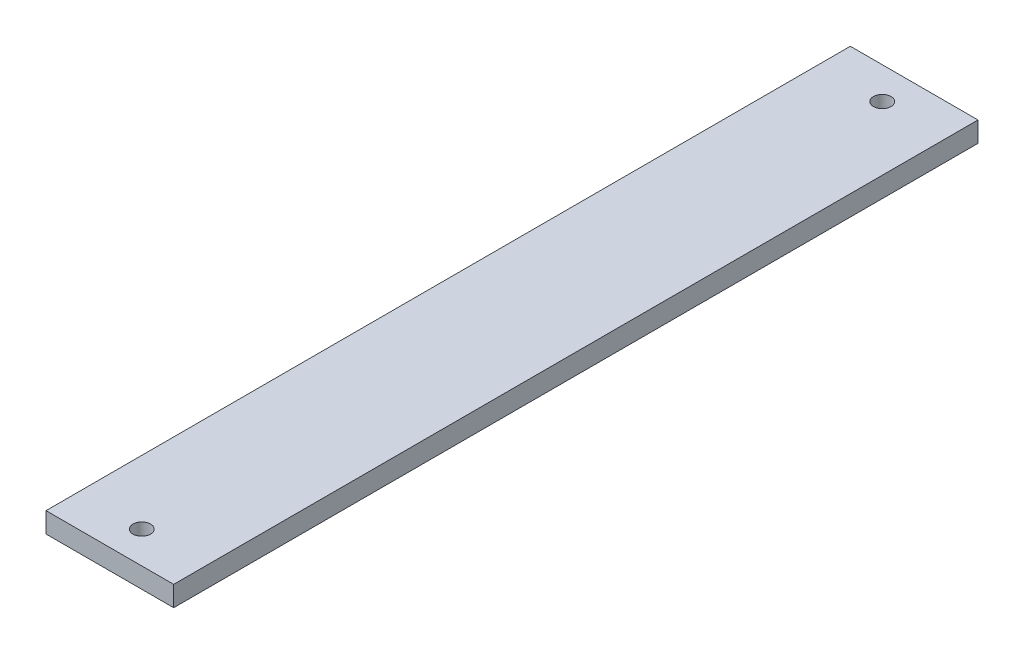
SolidWorks part; units mm, degrees
ref_plane "Front Plane" through (0, 0, 0) normal (0, 0, 1) x (1, 0, 0)
ref_plane "Top Plane" through (0, 0, 0) normal (0, 1, 0) x (1, 0, 0)
ref_plane "Right Plane" through (0, 0, 0) normal (1, 0, 0) x (0, 0, -1)
sketch "Sketch1" plane through (0, 0, 0) normal (0, 1, 0) x (1, 0, 0)
  line L0 (0, 0) -> (0, 116) construction
  line L1 (-20, -126) -> (20, -126)
  line L2 (-20, -126) -> (-20, 126)
  line L3 (-20, 126) -> (20, 126)
  line L4 (20, -126) -> (20, 126)
  line L5 (-20, -126) -> (20, 126) construction
  line L6 (-20, 126) -> (20, -126) construction
  line L7 (0, 0) -> (0, -116) construction
  circle A0 centre (0, 116) radius 2.75
  circle A1 centre (0, -116) radius 2.75
  point P0 (0, 0)
  dimension "D3" = 5.5
  dimension "D1" = 40
  dimension "D2" = 252
  dimension "D4" = 10
extrude "Boss-Extrude1" add sketch "Sketch1" along normal blind 6.35 contours L1 L4 L3 L2 A1 A0 region at (0, 0, 0)
